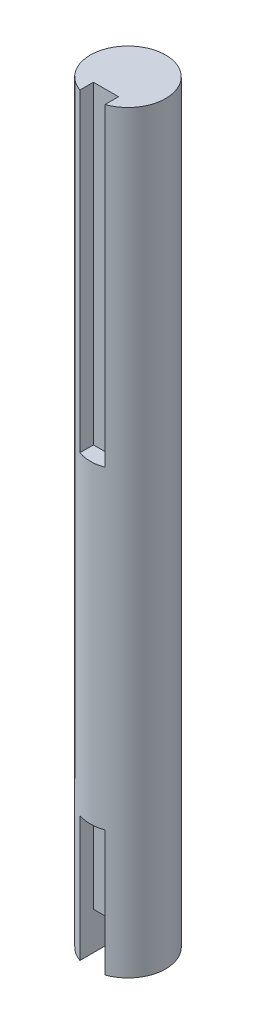
SolidWorks part; units mm, degrees
ref_plane "Front Plane" through (0, 0, 0) normal (0, 0, 1) x (1, 0, 0)
ref_plane "Top Plane" through (0, 0, 0) normal (0, 1, 0) x (1, 0, 0)
ref_plane "Right Plane" through (0, 0, 0) normal (1, 0, 0) x (0, 0, -1)
sketch "Sketch1" plane through (0, 0, 0) normal (0, 1, 0) x (1, 0, 0)
  circle A0 centre (0, 0) radius 6
  dimension "D1" = 12
extrude "Boss-Extrude1" add sketch "Sketch1" along normal blind 104 and the other way blind 16
sketch "Sketch2" plane through (0, 0, 0) normal (0, 1, 0) x (1, 0, 0)
  line L1 (-2, -8.5) -> (2, -8.5)
  line L2 (-2, -8.5) -> (-2, -3.5)
  line L3 (-2, -3.5) -> (2, -3.5)
  line L4 (2, -8.5) -> (2, -3.5)
  line L5 (-2, -8.5) -> (2, -3.5) construction
  line L6 (-2, -3.5) -> (2, -8.5) construction
  circle A0 centre (0, 0) radius 6 construction
  point P0 (0, -6)
  dimension "D1" = 2.5
  dimension "D2" = 4
extrude "Cut-Extrude3" cut sketch "Sketch2" against normal blind 0.0001 and the other way blind 20 from surface starting at face at (0, -16, 6)
extrude "Cut-Extrude4" cut sketch "Sketch2<2>" against normal blind 50 from surface starting at face at (0, 104, 6)
sketch "Sketch2<2>" plane through (0, 0, 0) normal (0, 1, 0) x (1, 0, 0) same geometry as "Sketch2"
sketch "Sketch3" plane through (0, 0, 0) normal (0, 1, 0) x (1, 0, 0)
  line L1 (-2, -11) -> (2, -11)
  line L2 (-2, -11) -> (-2, -1)
  line L3 (-2, -1) -> (2, -1)
  line L4 (2, -11) -> (2, -1)
  line L5 (-2, -11) -> (2, -1) construction
  line L6 (-2, -1) -> (2, -11) construction
  arc A0 (-2, -5.6569) -> (2, -5.6569) centre (0, 0) ccw construction
  point P0 (0, -6)
  dimension "D1" = 4
  dimension "D2" = 5
extrude "Cut-Extrude6" cut sketch "Sketch3" along normal blind 6 from surface starting at face at (0, -16, 1.6642)
sketch "Sketch4" plane through (0, 0, 0) normal (1, 0, 0) x (0, 0, -1)
  line L0 (0.1716, 107.721) -> (0.1716, -45.4994) construction
